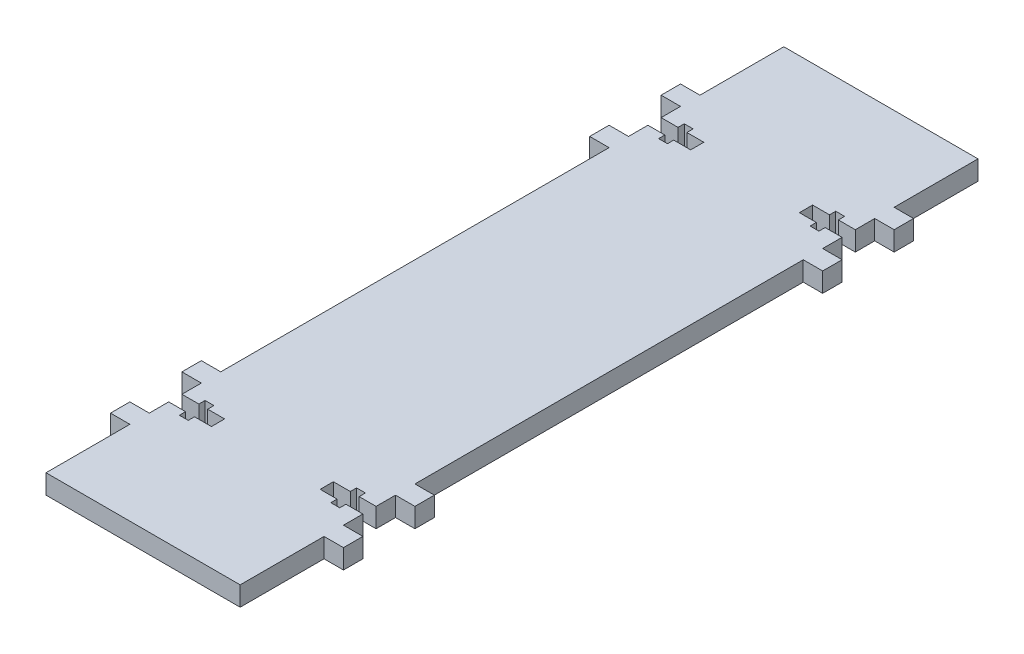
SolidWorks part; units mm, degrees
ref_plane "Front Plane" through (0, 0, 0) normal (0, 0, 1) x (1, 0, 0)
ref_plane "Top Plane" through (0, 0, 0) normal (0, 1, 0) x (1, 0, 0)
ref_plane "Right Plane" through (0, 0, 0) normal (1, 0, 0) x (0, 0, -1)
sketch "Elevator Belt Backplate" plane through (0, 0, 0) normal (0, 1, 0) x (1, 0, 0)
  line L0 (-31.75, -63.5) -> (-31.75, 63.5)
  line L1 (-31.75, -120.65) -> (31.75, -120.65)
  line L2 (-31.75, -93.218) -> (-31.75, -120.65)
  line L3 (-31.75, 120.65) -> (31.75, 120.65)
  line L4 (31.75, -120.65) -> (31.75, -93.218)
  line L5 (-31.75, -120.65) -> (31.75, 120.65) construction
  line L6 (-31.75, 120.65) -> (31.75, -120.65) construction
  line L7 (31.75, 93.218) -> (31.75, 120.65)
  line L9 (0, 120.65) -> (0, -120.65) construction
  line L21 (-31.75, 93.218) -> (-31.75, 120.65)
  line L70 (31.75, -63.5) -> (31.75, 63.5)
  point P0 (0, 0)
  line B0 (31.75, 69.85) -> (38.1, 69.85)
  line B1 (38.1, 69.85) -> (38.1, 63.5)
  line B2 (38.1, 63.5) -> (31.75, 63.5)
  line B3 (31.75, 76.2) -> (26.215, 76.2)
  line B4 (26.215, 76.2) -> (26.215, 74.159)
  line B5 (26.215, 74.159) -> (23.315, 74.159)
  line B6 (23.315, 74.159) -> (23.315, 76.2)
  line B7 (23.315, 76.2) -> (17.78, 76.2)
  line B8 (17.78, 76.2) -> (17.78, 80.518)
  line B9 (17.78, 80.518) -> (23.315, 80.518)
  line B10 (23.315, 80.518) -> (23.315, 82.559)
  line B11 (23.315, 82.559) -> (26.215, 82.559)
  line B12 (26.215, 82.559) -> (26.215, 80.518)
  line B13 (26.215, 80.518) -> (31.75, 80.518)
  line B14 (17.78, 78.359) -> (31.75, 78.359) construction
  line B15 (31.75, 86.868) -> (31.75, 80.518)
  line B16 (38.1, 93.218) -> (31.75, 93.218)
  line B17 (31.75, 69.85) -> (31.75, 76.2)
  line B18 (38.1, 86.868) -> (38.1, 93.218)
  line B19 (31.75, 86.868) -> (38.1, 86.868)
  line B20 (31.75, -69.85) -> (38.1, -69.85)
  line B21 (38.1, -69.85) -> (38.1, -63.5)
  line B22 (38.1, -63.5) -> (31.75, -63.5)
  line B23 (31.75, -76.2) -> (26.215, -76.2)
  line B24 (26.215, -76.2) -> (26.215, -74.159)
  line B25 (26.215, -74.159) -> (23.315, -74.159)
  line B26 (23.315, -74.159) -> (23.315, -76.2)
  line B27 (23.315, -76.2) -> (17.78, -76.2)
  line B28 (17.78, -76.2) -> (17.78, -80.518)
  line B29 (17.78, -80.518) -> (23.315, -80.518)
  line B30 (23.315, -80.518) -> (23.315, -82.559)
  line B31 (23.315, -82.559) -> (26.215, -82.559)
  line B32 (26.215, -82.559) -> (26.215, -80.518)
  line B33 (26.215, -80.518) -> (31.75, -80.518)
  line B34 (17.78, -78.359) -> (31.75, -78.359) construction
  line B35 (31.75, -86.868) -> (31.75, -80.518)
  line B36 (38.1, -93.218) -> (31.75, -93.218)
  line B37 (31.75, -69.85) -> (31.75, -76.2)
  line B38 (38.1, -86.868) -> (38.1, -93.218)
  line B39 (31.75, -86.868) -> (38.1, -86.868)
  line B40 (-31.75, -69.85) -> (-38.1, -69.85)
  line B41 (-38.1, -69.85) -> (-38.1, -63.5)
  line B42 (-38.1, -63.5) -> (-31.75, -63.5)
  line B43 (-31.75, -76.2) -> (-26.215, -76.2)
  line B44 (-26.215, -76.2) -> (-26.215, -74.159)
  line B45 (-26.215, -74.159) -> (-23.315, -74.159)
  line B46 (-23.315, -74.159) -> (-23.315, -76.2)
  line B47 (-23.315, -76.2) -> (-17.78, -76.2)
  line B48 (-17.78, -76.2) -> (-17.78, -80.518)
  line B49 (-17.78, -80.518) -> (-23.315, -80.518)
  line B50 (-23.315, -80.518) -> (-23.315, -82.559)
  line B51 (-23.315, -82.559) -> (-26.215, -82.559)
  line B52 (-26.215, -82.559) -> (-26.215, -80.518)
  line B53 (-26.215, -80.518) -> (-31.75, -80.518)
  line B54 (-17.78, -78.359) -> (-31.75, -78.359) construction
  line B55 (-31.75, -86.868) -> (-31.75, -80.518)
  line B56 (-38.1, -93.218) -> (-31.75, -93.218)
  line B57 (-31.75, -69.85) -> (-31.75, -76.2)
  line B58 (-38.1, -86.868) -> (-38.1, -93.218)
  line B59 (-31.75, -86.868) -> (-38.1, -86.868)
  line B60 (-31.75, 69.85) -> (-38.1, 69.85)
  line B61 (-38.1, 69.85) -> (-38.1, 63.5)
  line B62 (-38.1, 63.5) -> (-31.75, 63.5)
  line B63 (-31.75, 76.2) -> (-26.215, 76.2)
  line B64 (-26.215, 76.2) -> (-26.215, 74.159)
  line B65 (-26.215, 74.159) -> (-23.315, 74.159)
  line B66 (-23.315, 74.159) -> (-23.315, 76.2)
  line B67 (-23.315, 76.2) -> (-17.78, 76.2)
  line B68 (-17.78, 76.2) -> (-17.78, 80.518)
  line B69 (-17.78, 80.518) -> (-23.315, 80.518)
  line B70 (-23.315, 80.518) -> (-23.315, 82.559)
  line B71 (-23.315, 82.559) -> (-26.215, 82.559)
  line B72 (-26.215, 82.559) -> (-26.215, 80.518)
  line B73 (-26.215, 80.518) -> (-31.75, 80.518)
  line B74 (-17.78, 78.359) -> (-31.75, 78.359) construction
  line B75 (-31.75, 86.868) -> (-31.75, 80.518)
  line B76 (-38.1, 93.218) -> (-31.75, 93.218)
  line B77 (-31.75, 69.85) -> (-31.75, 76.2)
  line B78 (-38.1, 86.868) -> (-38.1, 93.218)
  line B79 (-31.75, 86.868) -> (-38.1, 86.868)
  dimension "D4" = 63.5
  dimension "D5" = 241.3
  dimension "D1" = 63.5
  dimension "D2" = 63.5
sketch_block_instance "Male T-slot assembly-1"
sketch_block "Male T-slot assembly" parameters "D1"=6.35, "D2"=6.35, "D3"=4.318, "D4"=2.9, "D5"=8.4, "D6"=13.97, "D7"=6.35
sketch_block_instance "Male T-slot assembly-3"
sketch_block_instance "Male T-slot assembly-10"
sketch_block_instance "Male T-slot assembly-11" parameters "D1"=108.2396, "D2"=10.8283, "D3"=15.6569, "D4"=108.2396, "D5"=107.7331, "D6"=6.35, "D7"=8.2716, "D8"=8.3408, "D9"=5.58, "D10"=5.535
extrude "Boss-Extrude1" add sketch "Elevator Belt Backplate" along normal blind 6.35 contours B79 B75 B73 B72 B71 B70 B69 B68 B67 B66 B65 B64 B63 B77 B60 B61 B62 L0 B42 B41 B40 B57 B43 B44 B45 B46 B47 B48 B49 B50 B51 B52 B53 B55 B59 B58 B56 L2 L1 L4 B36 B38 B39 B35 B33 B32 B31 B30 B29 B28 B27 region at (0, 0, 0)
equation "\"Ball Diameter\"= 1.75in"
equation "\"Sheet Thickness\"= 0.25in"
equation "\"Screw Diameter\"= .17in"
equation "\"Robot Diameter\"= 14in"
equation "\"Castor Screw Diameter\"= 0.22in"
equation "\"Wheel Diameter\" = 4in"
equation "\"Nut Diameter\" = 8.4mm"
equation "\"Nut Height\" = 2.9mm"
equation "\"Screw Height\" = 0.55in"
equation "\"Pulley Diameter\" = 1in"
equation "\"Reactor Height\" = 14in"
equation "\"Elevator Height\" = 11.5in"
equation "\"Elevator Width\" = \"Ball Diameter\" + 0.25in"
equation "\"Elevator Bearing Diameter\" = sqr(2*(\"Sheet Thickness\"^2)) + 0.2in"
equation "\"Elevator Axle Length\" = \"Elevator Width\" + 8*\"Sheet Thickness\""
equation "\"D7@Elevator Belt Backplate\"=\"Sheet Thickness\""
equation "\"D8@Elevator Belt Backplate\"=\"Sheet Thickness\""
equation "\"D4@Elevator Belt Backplate\"=\"Elevator Width\" + 2 * \"Sheet Thickness\""
equation "\"D5@Elevator Belt Backplate\"=\"Elevator Height\"-\"Pulley Diameter\"-1in"
equation "\"D1@Boss-Extrude1\"=\"Sheet Thickness\""
